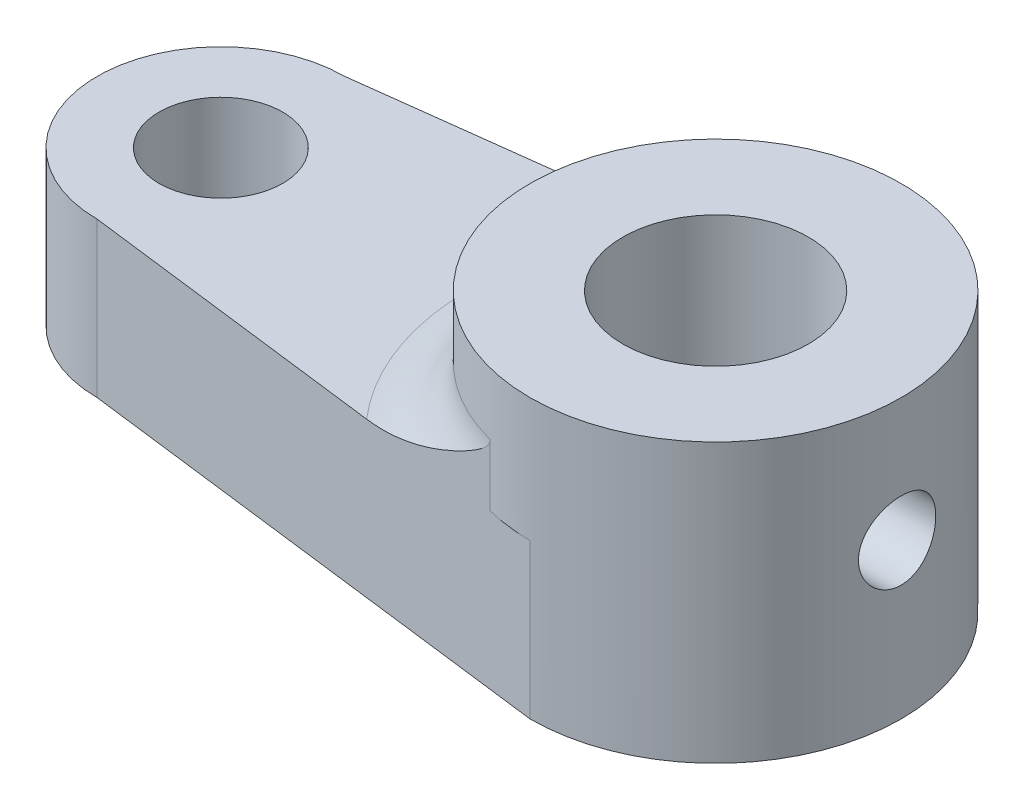
SolidWorks part; units mm, degrees
ref_plane "Front Plane" through (0, 0, 0) normal (0, 0, 1) x (1, 0, 0)
ref_plane "Top Plane" through (0, 0, 0) normal (0, 1, 0) x (1, 0, 0)
ref_plane "Right Plane" through (0, 0, 0) normal (1, 0, 0) x (0, 0, -1)
sketch "Sketch1" plane through (0, 0, 0) normal (0, 1, 0) x (1, 0, 0)
  line L1 (-51.4269, 4) -> (-35.4269, 6)
  line L2 (-51.4269, -4) -> (-35.4269, -6)
  circle A0 centre (-51.4269, 0) radius 2
  circle A1 centre (-35.4269, 0) radius 3
  circle A2 centre (-35.4269, 0) radius 6
  circle A3 centre (-51.4269, 0) radius 4
extrude "Boss-Extrude1" add sketch "Sketch1" along normal blind 5 contours A3 A0 | A3 L2 A2 L1 | L2 A2 L1 A1
sketch "Sketch2" plane through (0, 5, 0) normal (0, 1, 0) x (1, 0, 0)
  circle A0 centre (-35.4269, 0) radius 3 construction
  circle A1 centre (-35.4269, 0) radius 6 construction
  circle A2 centre (-35.4269, 0) radius 3
  circle A3 centre (-35.4269, 0) radius 6
extrude "Boss-Extrude2" add sketch "Sketch2" along normal blind 4
fillet "Fillet1" radius 2 1 edges at (-41.4269, 5, 0)
sketch "Sketch5" plane through (0, 0, 0) normal (0, 1, 0) x (1, 0, 0)
  line L0 (-28.127, 4.7508) -> (-28.127, -4.3906)
surface "Surface-Extrude1" sketch "Sketch5" parameters "D1"=10
hole_wizard "M3x0.5 Tapped Hole2" positions "Sketch6" profile "Sketch7" tap size "M3x0.5" standard "ANSI Metric"
sketch "Sketch6" plane through (-28.127, 0, 0) normal (-1, 0, 0) x (0, 0, 1)
  line L0 (-4.7508, 0) -> (4.3906, 0) construction
  point P0 (0, 5)
  dimension "D1" = 5
sketch "Sketch7" plane through (-28.127, 5, 0) normal (0, 1, 0) x (0, 0, -1)
  line L0 (0, 0) -> (0, 8.2511)
  line L1 (0, 8.2511) -> (1.25, 7.5)
  line L2 (1.25, 7.5) -> (1.25, 0)
  line L5 (1.25, 0) -> (0, 0)
  line L10 (0, 8.2511) -> (-1.25, 7.5) construction
  line L11 (0, -6.35) -> (0, 107.95) construction
  dimension "Tap Drill Dia." = 2.5
  dimension "Tap Drill Depth" = 7.5
  dimension "Drill Angle" = 118
cosmetic thread "Hole Thread2" parameters "D1"=6, "D2"=3
ref_plane "Plane1" through (10, 0, 0) normal (1, 0, 0) x (0, 0, -1)
